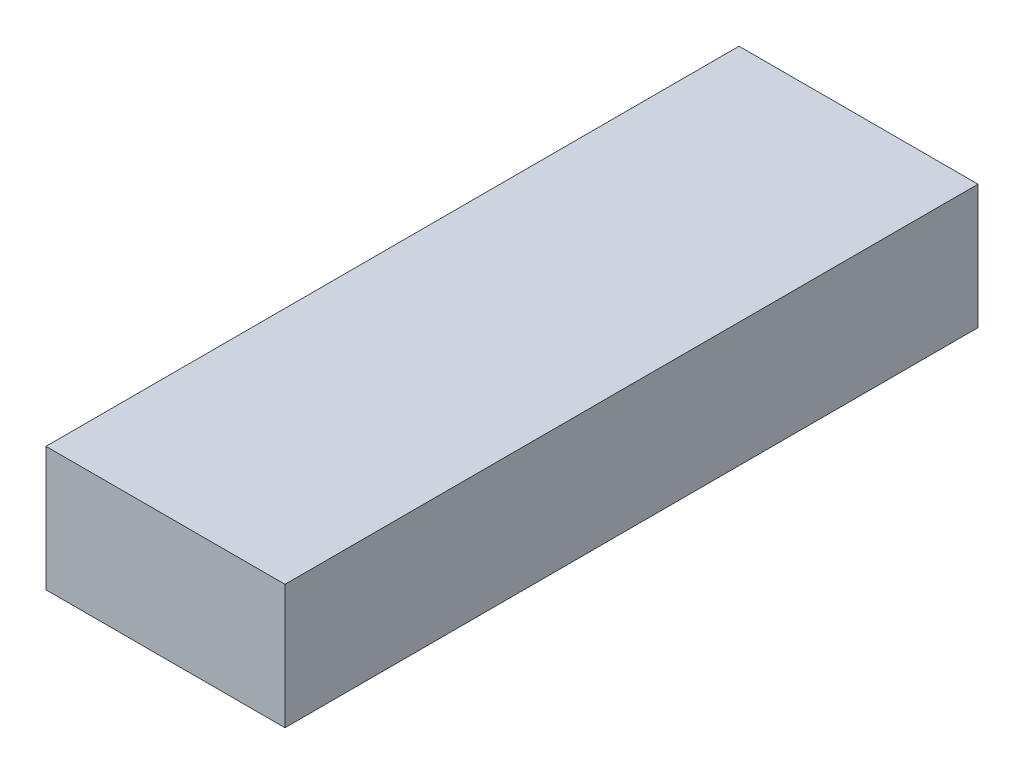
SolidWorks part; units mm, degrees
ref_plane "Alzado" through (0, 0, 0) normal (0, 0, 1) x (1, 0, 0)
ref_plane "Planta" through (0, 0, 0) normal (0, 1, 0) x (1, 0, 0)
ref_plane "Vista lateral" through (0, 0, 0) normal (1, 0, 0) x (0, 0, -1)
sketch "Croquis1" plane through (0, 0, 0) normal (0, 0, 1) x (1, 0, 0)
  line L1 (-5, -26) -> (-55, -26)
  line L2 (-5, -26) -> (-5, 0)
  line L3 (-5, 0) -> (-55, 0)
  line L4 (-55, -26) -> (-55, 0)
  dimension "D1" = 26
  dimension "D2" = 50
extrude "Saliente-Extruir1" add sketch "Croquis1" along normal blind 145
